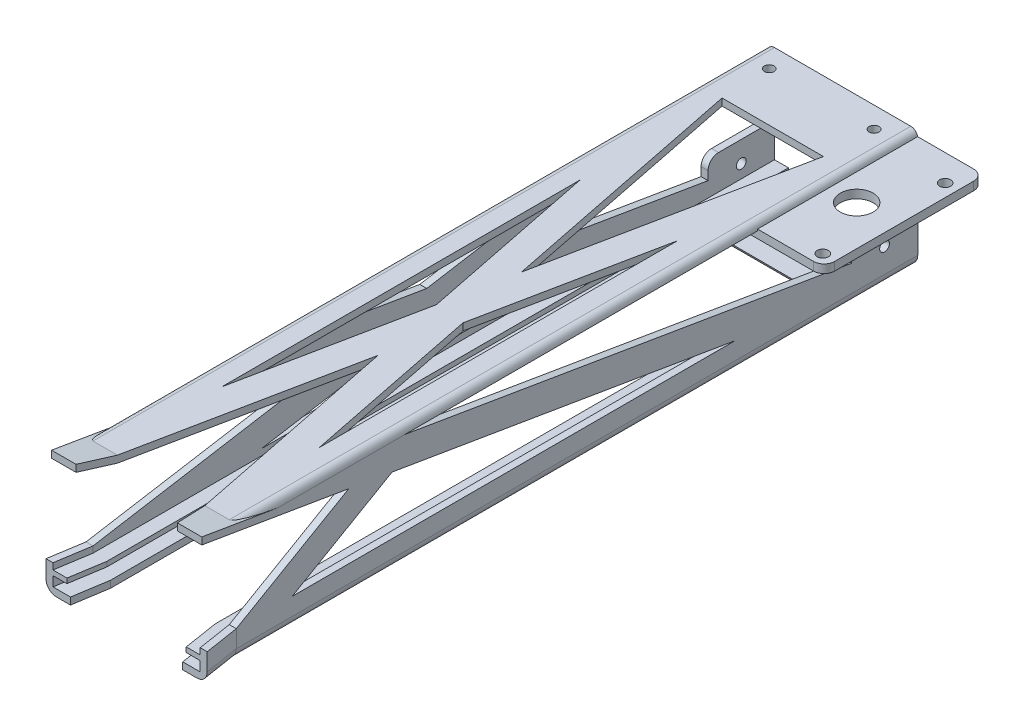
SolidWorks part; units mm, degrees
ref_plane "Front Plane" through (0, 0, 0) normal (0, 0, 1) x (1, 0, 0)
ref_plane "Top Plane" through (0, 0, 0) normal (0, 1, 0) x (1, 0, 0)
ref_plane "Right Plane" through (0, 0, 0) normal (1, 0, 0) x (0, 0, -1)
sketch "Sketch1" plane through (0, 0, 0) normal (0, 0, 1) x (1, 0, 0)
  line L0 (0, 7.6546) -> (0, -7.0531) construction
  line L1 (-19.5, -1) -> (19.5, -1)
  line L2 (-19.5, -1) -> (-19.5, 1)
  line L3 (-19.5, 1) -> (19.5, 1)
  line L4 (19.5, -1) -> (19.5, 1)
  line L5 (-19.5, -1) -> (19.5, 1) construction
  line L6 (-19.5, 1) -> (19.5, -1) construction
  line L7 (-19.5, -1) -> (-21.5, -1)
  line L8 (-19.5, -1) -> (-19.5, 5.2)
  line L9 (-19.5, 5.2) -> (-21.5, 5.2)
  line L10 (-21.5, -1) -> (-21.5, 5.2)
  line L11 (-19.5, 5.2) -> (-15.5, 5.2)
  line L12 (-19.5, 5.2) -> (-19.5, 3.8)
  line L13 (-19.5, 3.8) -> (-15.5, 3.8)
  line L14 (-15.5, 5.2) -> (-15.5, 3.8)
  line L15 (19.5, 3.8) -> (15.5, 3.8)
  line L16 (15.5, 5.2) -> (15.5, 3.8)
  line L17 (19.5, 5.2) -> (15.5, 5.2)
  line L18 (19.5, 5.2) -> (19.5, 3.8)
  line L19 (19.5, 5.2) -> (21.5, 5.2)
  line L20 (21.5, -1) -> (21.5, 5.2)
  line L21 (19.5, -1) -> (21.5, -1)
  line L22 (19.5, -1) -> (19.5, 5.2)
  line L23 (-19.5, 33) -> (-19.5, 31)
  line L24 (21.5, 5.2) -> (19.5, 5.2)
  line L25 (21.5, 5.2) -> (21.5, 33)
  line L26 (21.5, 33) -> (19.5, 33)
  line L27 (19.5, 5.2) -> (19.5, 33)
  line L28 (19.5, 33) -> (-19.5, 33)
  line L29 (19.5, 33) -> (19.5, 31)
  line L30 (19.5, 31) -> (-19.5, 31)
  line L31 (0, 33) -> (0, 31)
  line L32 (-21.5, 33) -> (-19.5, 33)
  line L33 (-19.5, 5.2) -> (-19.5, 33)
  line L34 (-21.5, 5.2) -> (-19.5, 5.2)
  line L35 (-21.5, 5.2) -> (-21.5, 33)
  point P0 (0, 0)
  dimension "D1" = 39
  dimension "D2" = 2
  dimension "D3" = 2
  dimension "D4" = 1.4
  dimension "D5" = 2.8
  dimension "D6" = 4
  dimension "D7" = 2
  dimension "D8" = 32
extrude "Boss-Extrude1" add sketch "Sketch1" along normal blind 195 contours L22 L4 L21 L20 L19 L18 | L18 L17 L16 L15 | L1 L4 L3 L2 | L10 L7 L2 L8 L9 | L14 L11 L8 L13 | L27 L19 L25 L26 | L28 L31 L30 L27 | L31 L28 L23 L30 | L35 L9 L33 L23 L32 region at (0, 0, 0) region at (-20.5, 2.1, 0) region at (20.5, 2.1, 0) region at (-17.5, 4.5, 0) region at (-20.5, 19.1, 0) region at (17.5, 4.5, 0) region at (20.5, 19.1, 0) region at (-9.75, 32, 0) region at (9.75, 32, 0)
sketch "Sketch2" plane through (21.5, 0, 0) normal (1, 0, 0) x (0, 0, -1)
  line L1 (-195, 31) -> (-4, 31)
  line L2 (-195, 31) -> (-195, 7)
  line L3 (-195, 7) -> (-4, 7)
  line L4 (-4, 31) -> (-4, 7)
  line L5 (0, -1) -> (0, 33) construction
  line L6 (-195, 33) -> (0, 33) construction
  line L7 (-195, -1) -> (0, -1) construction
  line L8 (-195, -1) -> (-195, 33) construction
  dimension "D1" = 2
  dimension "D2" = 8
  dimension "D3" = 4
  dimension "D4" = 0
extrude "Cut-Extrude1" cut sketch "Sketch2" against normal through all both and the other way through all
sketch "Sketch3" plane through (0, -1, 0) normal (0, -1, 0) x (-1, 0, 0)
  line L0 (21.5, 0) -> (-21.5, 0) construction
  line L1 (14.5, -215) -> (-14.5, -215)
  line L2 (14.5, -215) -> (14.5, 8)
  line L3 (14.5, 8) -> (-14.5, 8)
  line L4 (-14.5, -215) -> (-14.5, 8)
  line L5 (21.5, -195) -> (21.5, 0) construction
  line L6 (-21.5, -195) -> (-21.5, 0) construction
  line L7 (21.5, -195) -> (-21.5, -195) construction
  dimension "D1" = 8
  dimension "D2" = 7
  dimension "D3" = 7
  dimension "D4" = 20
extrude "Cut-Extrude2" cut sketch "Sketch3" against normal blind 2
sketch "Sketch5" plane through (21.5, 0, 0) normal (1, 0, 0) x (0, 0, -1)
  line L0 (0, -1) -> (0, 33) construction
  line L1 (0, 29) -> (-45.8, 29)
  line L2 (0, 29) -> (0, 33)
  line L3 (0, 33) -> (-45.8, 33)
  line L4 (-45.8, 29) -> (-45.8, 33)
  line L5 (-195, 33) -> (0, 33) construction
  dimension "D1" = 4
  dimension "D2" = 45.8
extrude "Boss-Extrude2" add sketch "Sketch5" against normal blind 2
sketch "Sketch6" plane through (21.5, 0, 0) normal (1, 0, 0) x (0, 0, -1)
  line L1 (-45.8, 29) -> (0, 29)
  line L2 (-45.8, 29) -> (-45.8, 31.4)
  line L3 (-45.8, 31.4) -> (0, 31.4)
  line L4 (0, 29) -> (0, 31.4)
  line L9 (0, -1) -> (0, 33) construction
  dimension "D2" = 2.4
sketch "Sketch8" plane through (21.5, 0, 0) normal (1, 0, 0) x (0, 0, -1)
  line L1 (-4, 7) -> (-19, 7)
  line L2 (-4, 7) -> (-4, 15)
  line L3 (-4, 15) -> (-19, 15)
  line L4 (-19, 7) -> (-19, 15)
  dimension "D1" = 8
  dimension "D2" = 15
extrude "Boss-Extrude4" add sketch "Sketch8" against normal blind 2
sketch "Sketch9" plane through (-21.5, 0, 0) normal (-1, 0, 0) x (0, 0, 1)
  line L1 (4, 7) -> (19, 7)
  line L2 (4, 7) -> (4, 15)
  line L3 (4, 15) -> (19, 15)
  line L4 (19, 7) -> (19, 15)
  dimension "D1" = 15
  dimension "D2" = 8
extrude "Boss-Extrude5" add sketch "Sketch9" against normal blind 2
sketch "Sketch10" plane through (-21.5, 0, 0) normal (-1, 0, 0) x (0, 0, 1)
  line L0 (4, 31) -> (146.7491, 7)
  line L2 (4, 31) -> (52.2509, 31)
  line L3 (146.7491, 7) -> (195, 7)
  line L5 (52.2509, 31) -> (195, 7)
  line L6 (195, 7) -> (19, 7) construction
  line L7 (195, 31) -> (52.2509, 7)
  line L8 (195, 31) -> (146.7491, 31)
  line L9 (52.2509, 7) -> (4, 7)
  line L10 (146.7491, 31) -> (4, 7)
  line L11 (4, 15) -> (4, 31) construction
  dimension "D1" = 8
  dimension "D2" = 8
extrude "Boss-Extrude6" add sketch "Sketch10" against normal blind 2 contours L7 L9 L10 L8 | L5 L3 L0 L2
sketch "Sketch13" plane through (21.5, 0, 0) normal (1, 0, 0) x (0, 0, -1)
  line L0 (-195, 31) -> (-146.7491, 31)
  line L1 (-195, 31) -> (-52.2509, 7)
  line L2 (-146.7491, 31) -> (-4, 7)
  line L3 (-52.2509, 7) -> (-4, 7)
  line L4 (-195, 31) -> (-45.8, 31) construction
  line L5 (-19, 7) -> (-195, 7) construction
  line L6 (-4, 29) -> (-4, 15) construction
  line L7 (-195, 7) -> (-179, 7)
  line L8 (-195, 7) -> (-162.8059, 25.5873)
  line L9 (-179, 7) -> (-146.8059, 25.5873)
  line L10 (-162.8059, 25.5873) -> (-146.8059, 25.5873)
  line M5 (-19, 15) -> (-19, 7)
  line M6 (-19, 7) -> (-195, 7)
  line M12 (-195, 31) -> (-45.8, 31)
  dimension "D1" = 8
  dimension "D2" = 150
  dimension "D3" = 8
extrude "Boss-Extrude9" add sketch "Sketch6" along normal blind 19
sketch "Sketch14" plane through (0, 29, 0) normal (0, -1, 0) x (-1, 0, 0)
  line L0 (-19.5, -45.8) -> (-40.5, -45.8) construction
  line L1 (-36.8827, -42.55) -> (-36.8827, -7.55)
  circle A0 centre (-36.8827, -42.55) radius 1.6
  circle A1 centre (-36.8827, -7.55) radius 1.6
  circle A2 centre (-29.0827, -25.05) radius 4.7
  point P4 (-36.8827, -25.05)
  dimension "D1" = 3.2
  dimension "D2" = 3.2
  dimension "D6" = 9.4
  dimension "D3" = 35
  dimension "D4" = 3.25
  dimension "D5" = 7.8
extrude "Cut-Extrude3" cut sketch "Sketch14" against normal blind 19 contours A2 | A0 | A1 region at (29.0827, 29, 25.05)
hole_wizard "Tap Drill for M3x0.5 Tap1" positions "3DSketch2" profile "Sketch17" hole size "M3x0.5" standard "ANSI Metric"
sketch3d "3DSketch2"
  line L0 (-21.5, -1, 0) -> (-21.5, 33, 0) construction
  line L1 (-21.5, 15, 19) -> (-21.5, 15, 4) construction
  line L2 (21.5, 15, 4) -> (21.5, 15, 19) construction
  line L3 (21.5, -1, 0) -> (21.5, 29, 0) construction
  point P0 (-21.5, 9, 9.5)
  point P7 (21.5, 9, 9.5)
  dimension "D1" = 9.5
  dimension "D2" = 6
  dimension "D3" = 6
  dimension "D4" = 9.5
sketch "Sketch17" plane through (-21.5, 9, 9.5) normal (0, 1, 0) x (0, 0, 1)
  line L0 (0, 0) -> (0, 10.8412)
  line L1 (0, 10.8412) -> (1.4, 10)
  line L2 (1.4, 10) -> (1.4, 0)
  line L5 (1.4, 0) -> (0, 0)
  line L10 (0, 10.8412) -> (-1.4, 10) construction
  line L11 (0, -6.35) -> (0, 107.95) construction
  dimension "Hole Dia." = 2.8
  dimension "Hole Depth" = 10
  dimension "Drill Angle" = 118
hole_wizard "Tap Drill for M3x0.5 Tap2" positions "3DSketch3" profile "Sketch19" hole size "M3x0.5" standard "ANSI Metric"
sketch3d "3DSketch3"
  line L0 (15, 33, 6) -> (-15, 33, 6)
  line L2 (21.5, 33, 0) -> (-21.5, 33, 0) construction
  point P0 (15, 33, 6)
  point P2 (-15, 33, 6)
  point P8 (0, 33, 6)
  point P11 (0, 33, 0)
  dimension "D1" = 30
  dimension "D2" = 6
sketch "Sketch19" plane through (15, 33, 6) normal (1, 0, 0) x (0, 0, 1)
  line L0 (0, 0) -> (0, 10.8412)
  line L1 (0, 10.8412) -> (1.4, 10)
  line L2 (1.4, 10) -> (1.4, 0)
  line L5 (1.4, 0) -> (0, 0)
  line L10 (0, 10.8412) -> (-1.4, 10) construction
  line L11 (0, -6.35) -> (0, 107.95) construction
  dimension "Hole Dia." = 2.8
  dimension "Hole Depth" = 10
  dimension "Drill Angle" = 118
extrude "Boss-Extrude10" add sketch "Sketch13" against normal blind 2 contours L9 L1 L8 M6 | L1 L10 L9 L2 M6 M5 M12 | L10 L1 L9 region at (21.5, 19.1005, 100.1413) region at (21.5, 24.8928, 153.342) region at (21.5, 15.7831, 171.9455)
sketch "Sketch21" plane through (0, 0, 195) normal (0, 0, 1) x (1, 0, 0)
  line L0 (19.5, 31) -> (21.5, 31) construction
  line L1 (21.5, 31) -> (21.5, 33) construction
  line L2 (21.5, 33) -> (-21.5, 33) construction
  line L3 (-21.5, 33) -> (-21.5, 31) construction
  line L4 (-21.5, 31) -> (-19.5, 31) construction
  line L5 (-19.5, 31) -> (19.5, 31) construction
  line L6 (14.5, 1) -> (14.5, -1) construction
  line L7 (14.5, -1) -> (21.5, -1) construction
  line L8 (21.5, -1) -> (21.5, 7) construction
  line L9 (21.5, 7) -> (19.5, 7) construction
  line L10 (19.5, 7) -> (19.5, 5.2) construction
  line L11 (19.5, 5.2) -> (15.5, 5.2) construction
  line L12 (15.5, 5.2) -> (15.5, 3.8) construction
  line L13 (15.5, 3.8) -> (19.5, 3.8) construction
  line L14 (19.5, 3.8) -> (19.5, 1) construction
  line L15 (19.5, 1) -> (14.5, 1) construction
  line L16 (-14.5, -1) -> (-14.5, 1) construction
  line L17 (-14.5, 1) -> (-19.5, 1) construction
  line L18 (-19.5, 1) -> (-19.5, 3.8) construction
  line L19 (-19.5, 3.8) -> (-15.5, 3.8) construction
  line L20 (-15.5, 3.8) -> (-15.5, 5.2) construction
  line L21 (-15.5, 5.2) -> (-19.5, 5.2) construction
  line L22 (-19.5, 5.2) -> (-19.5, 7) construction
  line L23 (-19.5, 7) -> (-21.5, 7) construction
  line L24 (-21.5, 7) -> (-21.5, -1) construction
  line L25 (-21.5, -1) -> (-14.5, -1) construction
  line L26 (19.5, 31) -> (21.5, 31)
  line L27 (21.5, 31) -> (21.5, 33)
  line L28 (21.5, 33) -> (-21.5, 33)
  line L29 (-21.5, 33) -> (-21.5, 31)
  line L30 (-21.5, 31) -> (-19.5, 31)
  line L31 (-19.5, 31) -> (19.5, 31)
  line L32 (14.5, 1) -> (14.5, -1)
  line L33 (14.5, -1) -> (21.5, -1)
  line L34 (21.5, -1) -> (21.5, 7)
  line L35 (21.5, 7) -> (19.5, 7)
  line L36 (19.5, 7) -> (19.5, 5.2)
  line L37 (19.5, 5.2) -> (15.5, 5.2)
  line L38 (15.5, 5.2) -> (15.5, 3.8)
  line L39 (15.5, 3.8) -> (19.5, 3.8)
  line L40 (19.5, 3.8) -> (19.5, 1)
  line L41 (19.5, 1) -> (14.5, 1)
  line L42 (-14.5, -1) -> (-14.5, 1)
  line L43 (-14.5, 1) -> (-19.5, 1)
  line L44 (-19.5, 1) -> (-19.5, 3.8)
  line L45 (-19.5, 3.8) -> (-15.5, 3.8)
  line L46 (-15.5, 3.8) -> (-15.5, 5.2)
  line L47 (-15.5, 5.2) -> (-19.5, 5.2)
  line L48 (-19.5, 5.2) -> (-19.5, 7)
  line L49 (-19.5, 7) -> (-21.5, 7)
  line L50 (-21.5, 7) -> (-21.5, -1)
  line L51 (-21.5, -1) -> (-14.5, -1)
extrude "Boss-Extrude11" add sketch "Sketch21" along direction (0, -0.1658, -0.9862) on the side of the normal blind 10 contours L30 L31 L26 L27 L28 L29 region at (0, 32, 195)
sketch "Sketch22" plane through (0, -1, 0) normal (0, -1, 0) x (-1, 0, 0)
  line L0 (21.5, -195) -> (14.5, -150.8037)
  line L1 (14.5, -195) -> (14.5, 0) construction
  line L2 (21.5, -195) -> (21.5, 0) construction
  line L3 (-14.5, -150.8037) -> (-21.5, -195)
  line L4 (-14.5, 0) -> (-14.5, -195) construction
  line L6 (-21.5, -195) -> (-21.5, 0) construction
  dimension "D1" = 9
  dimension "D2" = 9
sketch "Sketch23" plane through (0, -1, 0) normal (0, -1, 0) x (-1, 0, 0)
  line L0 (21.5, 0) -> (14.5, 0) construction
  line L1 (18, 0) -> (-18, 0)
  line L2 (18, 0) -> (18, -20)
  line L3 (18, -20) -> (-18, -20)
  line L4 (-18, 0) -> (-18, -20)
  line L5 (14.5, -195) -> (14.5, 0) construction
  line L6 (-14.5, 0) -> (-14.5, -195) construction
  dimension "D1" = 3.5
  dimension "D2" = 3.5
  dimension "D3" = 20
extrude "Boss-Extrude12" add sketch "Sketch23" along normal blind 3 and the other way blind 1
fillet "Fillet3" radius 3 3 edges at (18, -4, 10) (0, -4, 20) (-18, -4, 10)
fillet "Fillet4" radius 3 2 edges at (-21.5, -1, 97.5) (21.5, -1, 97.5)
fillet "Fillet5" radius 3 2 edges at (20.5, 15, 19) (-20.5, 15, 19)
fillet "Fillet6" radius 3 2 edges at (40.5, 30.2, 0) (40.5, 30.2, 45.8)
chamfer "Chamfer3" distance 8 angle 10 1 edges at (0, 0, 20) first distance on face at (0, 0, 10)
sketch "Sketch25" plane through (-14.5, 0, 0) normal (1, 0, 0) x (0, 0, -1)
  line L0 (-195, -1) -> (-213.6366, 2.0529)
  line L4 (-195, -1) -> (-20, -1) construction
  dimension "D1" = 189.303
sketch "Sketch24" plane through (0, 0, 195) normal (0, 0, 1) x (1, 0, 0)
  line L0 (14.5, -1) -> (18.5, -1) construction
  line L1 (21.5, 2) -> (21.5, 7) construction
  line L2 (21.5, 7) -> (19.5, 7) construction
  line L3 (19.5, 7) -> (19.5, 5.2) construction
  line L4 (19.5, 5.2) -> (15.5, 5.2) construction
  line L5 (15.5, 5.2) -> (15.5, 3.8) construction
  line L6 (15.5, 3.8) -> (19.5, 3.8) construction
  line L7 (19.5, 3.8) -> (19.5, 1) construction
  line L8 (19.5, 1) -> (14.5, 1) construction
  line L9 (14.5, 1) -> (14.5, -1) construction
  line L10 (-21.5, 7) -> (-21.5, 2) construction
  line L11 (-18.5, -1) -> (-14.5, -1) construction
  line L12 (-14.5, -1) -> (-14.5, 1) construction
  line L13 (-14.5, 1) -> (-19.5, 1) construction
  line L14 (-19.5, 1) -> (-19.5, 3.8) construction
  line L15 (-19.5, 3.8) -> (-15.5, 3.8) construction
  line L16 (-15.5, 3.8) -> (-15.5, 5.2) construction
  line L17 (-15.5, 5.2) -> (-19.5, 5.2) construction
  line L18 (-19.5, 5.2) -> (-19.5, 7) construction
  line L19 (-19.5, 7) -> (-21.5, 7) construction
  line L20 (14.5, -1) -> (18.5, -1)
  line L21 (21.5, 2) -> (21.5, 7)
  line L22 (21.5, 7) -> (19.5, 7)
  line L23 (19.5, 7) -> (19.5, 5.2)
  line L24 (19.5, 5.2) -> (15.5, 5.2)
  line L25 (15.5, 5.2) -> (15.5, 3.8)
  line L26 (15.5, 3.8) -> (19.5, 3.8)
  line L27 (19.5, 3.8) -> (19.5, 1)
  line L28 (19.5, 1) -> (14.5, 1)
  line L29 (14.5, 1) -> (14.5, -1)
  line L30 (-21.5, 7) -> (-21.5, 2)
  line L31 (-18.5, -1) -> (-14.5, -1)
  line L32 (-14.5, -1) -> (-14.5, 1)
  line L33 (-14.5, 1) -> (-19.5, 1)
  line L34 (-19.5, 1) -> (-19.5, 3.8)
  line L35 (-19.5, 3.8) -> (-15.5, 3.8)
  line L36 (-15.5, 3.8) -> (-15.5, 5.2)
  line L37 (-15.5, 5.2) -> (-19.5, 5.2)
  line L38 (-19.5, 5.2) -> (-19.5, 7)
  line L39 (-19.5, 7) -> (-21.5, 7)
  arc A0 (18.5, -1) -> (21.5, 2) centre (18.5, 2) ccw construction
  arc A1 (-21.5, 2) -> (-18.5, -1) centre (-18.5, 2) ccw construction
  arc A2 (18.5, -1) -> (21.5, 2) centre (18.5, 2) ccw
  arc A3 (-21.5, 2) -> (-18.5, -1) centre (-18.5, 2) ccw
extrude "Boss-Extrude14" add sketch "Sketch24" along direction (0.1564, 0, -0.9877) on the side of the normal blind 10 contours L30 A3 L31 L32 L33 L34 L35 L36 L37 L38 L39
sketch "Sketch26" plane through (0, 0, 195) normal (0, 0, 1) x (1, 0, 0)
  line L10 (14.5, -1) -> (18.5, -1)
  line L11 (21.5, 2) -> (21.5, 7)
  line L12 (21.5, 7) -> (19.5, 7)
  line L13 (19.5, 7) -> (19.5, 5.2)
  line L14 (19.5, 5.2) -> (15.5, 5.2)
  line L15 (15.5, 5.2) -> (15.5, 3.8)
  line L16 (15.5, 3.8) -> (19.5, 3.8)
  line L17 (19.5, 3.8) -> (19.5, 1)
  line L18 (19.5, 1) -> (14.5, 1)
  line L19 (14.5, 1) -> (14.5, -1)
  line L20 (14.5, -1) -> (18.5, -1)
  line L21 (21.5, 2) -> (21.5, 7)
  line L22 (21.5, 7) -> (19.5, 7)
  line L23 (19.5, 7) -> (19.5, 5.2)
  line L24 (19.5, 5.2) -> (15.5, 5.2)
  line L25 (15.5, 5.2) -> (15.5, 3.8)
  line L26 (15.5, 3.8) -> (19.5, 3.8)
  line L27 (19.5, 3.8) -> (19.5, 1)
  line L28 (19.5, 1) -> (14.5, 1)
  line L29 (14.5, 1) -> (14.5, -1)
  arc A1 (18.5, -1) -> (21.5, 2) centre (18.5, 2) ccw
  arc A2 (18.5, -1) -> (21.5, 2) centre (18.5, 2) ccw
  dimension "D1" = 0
extrude "Boss-Extrude15" add sketch "Sketch26" along direction (0.1564, 0, 0.9877) on the side of the normal blind 10
sketch "Sketch27" plane through (0, 33, 0) normal (0, 1, 0) x (1, 0, 0)
  line L36 (14.5, -204.8616) -> (14.5, -164.2675)
  line L37 (14.5, -204.8616) -> (-14.5, -60.594)
  line L38 (14.5, -164.2675) -> (-14.5, -20)
  line L39 (-14.5, -60.594) -> (-14.5, -20)
  line L44 (14.5, -282.7407) -> (14.5, 38.3973)
  line L45 (-14.5, -299.6773) -> (-14.5, 33.9239)
  line L46 (21.5, -195) -> (21.5, 0) construction
  line L47 (-21.5, -195) -> (-21.5, 0) construction
  line L48 (21.5, 0) -> (-21.5, 0) construction
  line L53 (14.5, -20) -> (-14.5, -20)
  line L54 (-8.1424, -204.8616) -> (-14.5, -204.8616)
  line L55 (21.5, -204.8616) -> (-21.5, -204.8616) construction
  line L56 (14.5, -20) -> (14.5, -61.6831)
  line L57 (14.5, -20) -> (-14.5, -163.1785)
  line L58 (14.5, -61.6831) -> (-14.5, -204.8616)
  line L59 (-14.5, -163.1785) -> (-14.5, -204.8616)
  line L60 (14.5, -204.8616) -> (-14.5, -204.8616)
  line M47 (-21.5, -195) -> (21.5, -195)
  dimension "D2" = 7
  dimension "D3" = 7
  dimension "D9" = 8
  dimension "D14" = 20
fillet "Fillet7" radius 2 2 edges at (21.5, 33, 97.5) (-21.5, 33, 97.5)
extrude "Cut-Extrude6" cut sketch "Sketch27" against normal blind 10 and the other way blind 10 contours L44 L58 L38 | L57 L37 L45 | L37 L58 M47 | L60 L37 L58 L54 M47 | L57 L53 L38 region at (0.0037, 33, 200.0519) region at (0.0233, 33, 174.3337) region at (11.0501, 33, 112.9105) region at (-11.0501, 33, 111.9511) region at (-0.0183, 33, 43.9535)
sketch "Sketch28" plane through (0, 0, 0) normal (0, 1, 0) x (1, 0, 0)
  line L1 (14.5, 0) -> (-14.5, 0)
  line L2 (14.5, 0) -> (14.5, -20)
  line L3 (14.5, -20) -> (-14.5, -20)
  line L4 (-14.5, 0) -> (-14.5, -20)
  point P5 (0, 0)
extrude "Cut-Extrude7" cut sketch "Sketch28" against normal blind 2
equation "\"WallThickness\"=2"
equation "\"D3@Sketch1\"=\"WallThickness\""
equation "\"D7@Sketch1\"=\"WallThickness\""
equation "\"D2@Sketch1\"=\"WallThickness\""
equation "\"D1@Cut-Extrude2\"=\"WallThickness\""
equation "\"D1@Boss-Extrude6\"=\"WallThickness\""
equation "\"D1@Boss-Extrude5\"=\"WallThickness\""
equation "\"D1@Boss-Extrude2\"=\"WallThickness\""
equation "\"D1@Boss-Extrude4\"=\"WallThickness\""
equation "\"D1@Boss-Extrude10\"=\"WallThickness\""
